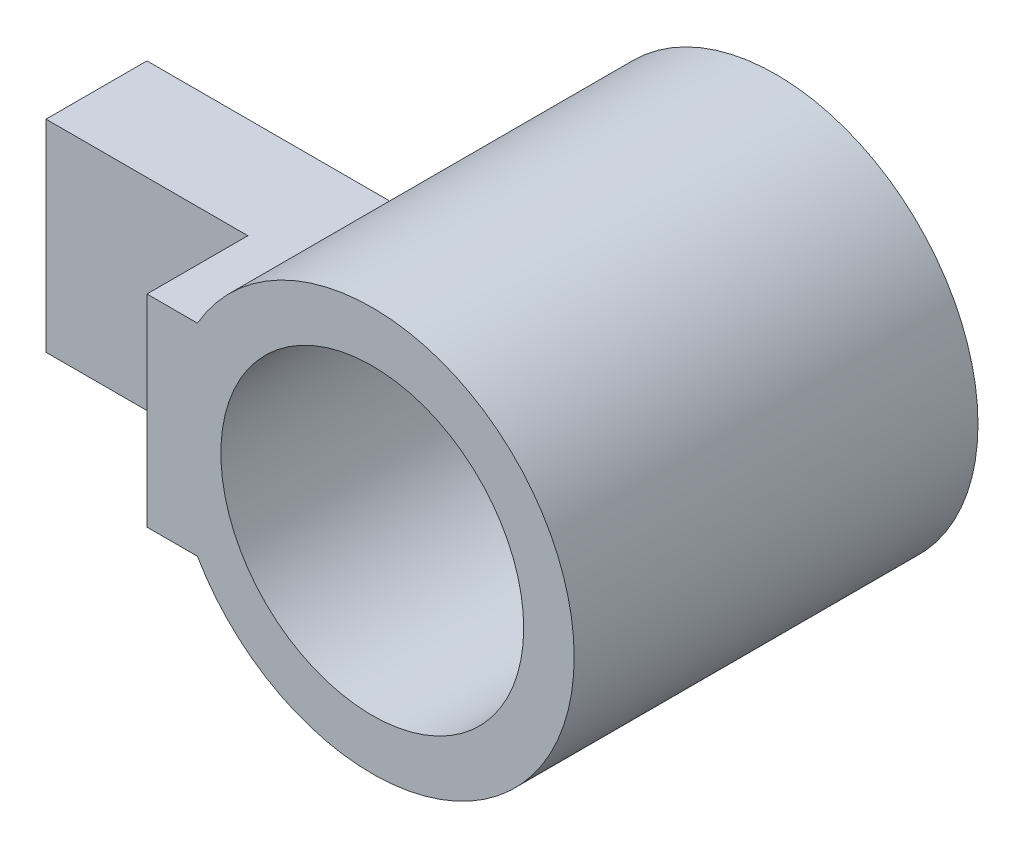
SolidWorks part; units mm, degrees
ref_plane "Alzado" through (0, 0, 0) normal (0, 0, 1) x (1, 0, 0)
ref_plane "Planta" through (0, 0, 0) normal (0, 1, 0) x (1, 0, 0)
ref_plane "Vista lateral" through (0, 0, 0) normal (1, 0, 0) x (0, 0, -1)
sketch "Croquis1" plane through (0, 0, 0) normal (0, 0, 1) x (1, 0, 0)
  circle A0 centre (0, 0) radius 20
  dimension "D1" = 40
extrude "Saliente-Extruir1" add sketch "Croquis1" along normal mid plane 40
sketch "Croquis6" plane through (0, 0, 20) normal (0, 0, 1) x (1, 0, 0)
  circle A0 centre (0, 0) radius 15
  dimension "D1" = 30
extrude "Cortar-Extruir1" cut sketch "Croquis6" against normal through all
sketch "Croquis7" plane through (0, 0, 20) normal (0, 0, 1) x (1, 0, 0)
  line L0 (0, 0) -> (-17.3205, 0) construction
  line L1 (-17.3205, 10) -> (-17.3205, -10)
  line L2 (-17.3205, 10) -> (-42.3205, 10)
  line L3 (-42.3205, 10) -> (-42.3205, -10)
  line L4 (-42.3205, -10) -> (-17.3205, -10)
  line L5 (0, 0) -> (0, 10) construction
  circle A0 centre (0, 0) radius 20 construction
  point P8 (-17.3205, 0)
  dimension "D1" = 20
  dimension "D2" = 25
extrude "Saliente-Extruir3" add sketch "Croquis7" against normal blind 20
sketch "Croquis8" plane through (0, 0, 20) normal (0, 0, -1) x (-1, 0, 0)
  line L0 (42.3205, 10) -> (22.3205, 10)
  line L1 (17.3205, 10) -> (42.3205, 10) construction
  line L2 (22.3205, 10) -> (22.3205, -10)
  line L3 (42.3205, -10) -> (17.3205, -10) construction
  line L4 (22.3205, -10) -> (42.3205, -10)
  line L5 (42.3205, -10) -> (42.3205, 10)
  line L6 (0, 0) -> (0, 10) construction
  line L7 (-22.3205, -10) -> (-42.3205, -10)
  line L8 (-22.3205, 10) -> (-22.3205, -10)
  line L9 (-42.3205, 10) -> (-22.3205, 10)
  line L10 (-42.3205, -10) -> (-42.3205, 10)
  dimension "D1" = 20
extrude "Cortar-Extruir2" cut sketch "Croquis8" along normal blind 10
